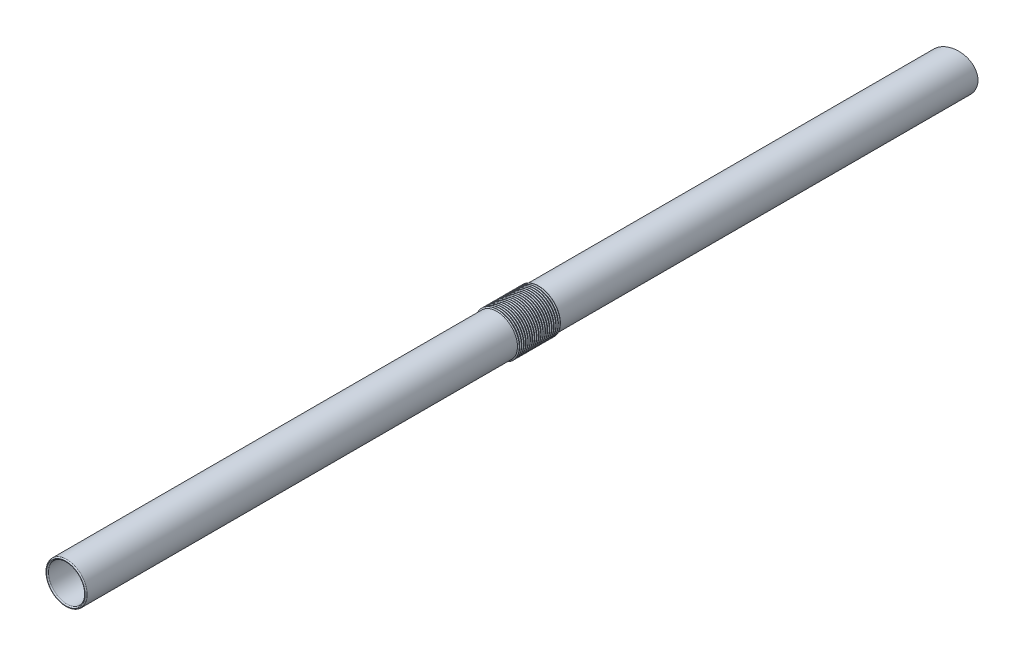
SolidWorks part; units mm, degrees
material "1023 Carbon Steel Sheet (SS)"
ref_plane "Front Plane" through (0, 0, 0) normal (0, 0, 1) x (1, 0, 0)
ref_plane "Top Plane" through (0, 0, 0) normal (0, 1, 0) x (1, 0, 0)
ref_plane "Right Plane" through (0, 0, 0) normal (1, 0, 0) x (0, 0, -1)
sketch "Sketch1" plane through (0, 0, 0) normal (0, 0, 1) x (1, 0, 0)
  circle A0 centre (0, 0) radius 9.5
  dimension "D1" = 19
extrude "Boss-Extrude1" add sketch "Sketch1" along normal mid plane 415
shell "Shell1" thickness 1 removed face at (9.5, 0, -207.5) removed face at (9.5, 0, 207.5)
sketch "Sketch2" plane through (0, 0, 0) normal (0, 1, 0) x (1, 0, 0)
  line L0 (9.5, 207.5) -> (-9.5, 202.409)
  line L1 (9.5, 207.5) -> (-9.5, 207.5) construction
  line L2 (9.5, 207.5) -> (-9.5, 207.5)
  line L3 (-9.5, 207.5) -> (-9.5, -207.5) construction
  line L4 (-9.5, 207.5) -> (-9.5, 202.409)
  dimension "D1" = 15
extrude "Cut-Extrude1" cut sketch "Sketch2" against normal mid plane 30
ref_plane "Plane1" through (0, 0, -2.7) normal (0, 0, 1) x (1, 0, 0)
sketch "Sketch4" plane through (0, 0, -2.7) normal (0, 0, 1) x (1, 0, 0)
  circle A0 centre (0, 0) radius 9.5 construction
  circle A1 centre (0, 0) radius 9.5
thread "Thread1" pitch 1 method extrude profile "Thread Profile1" start angle 0, offset 200.2, length 20, pitch 1, diameter 19
ref_plane "Plane2" through (-9.5, 0, 7.3) normal (0, -1, 0) x (-1, 0, 0)
sketch "Thread Profile1" plane through (-9.5, 0, 7.3) normal (0, -1, 0) x (-1, 0, 0)
  line L0 (0, 0) -> (0, 1) construction
  line L1 (0, 0) -> (0.5413, 0.3125)
  line L2 (0.5413, 0.3125) -> (0.5413, 0.4375)
  line L3 (0.5413, 0.4375) -> (0, 0.75)
  line L4 (0.5413, 0.375) -> (0, 0.375) construction
  line L11 (0, 0) -> (0, 0.75)
  point P2 (0, 0)
  dimension "Pitch" = 1
  dimension "Profile_Angle" = 60
  dimension "Profile_Land" = 0.125
  dimension "Profile_Height" = 0.5413
fillet "Fillet1" radius 0.5 2 edges at (8.5, 0, 207.5) (9.5, 0, 207.5)
